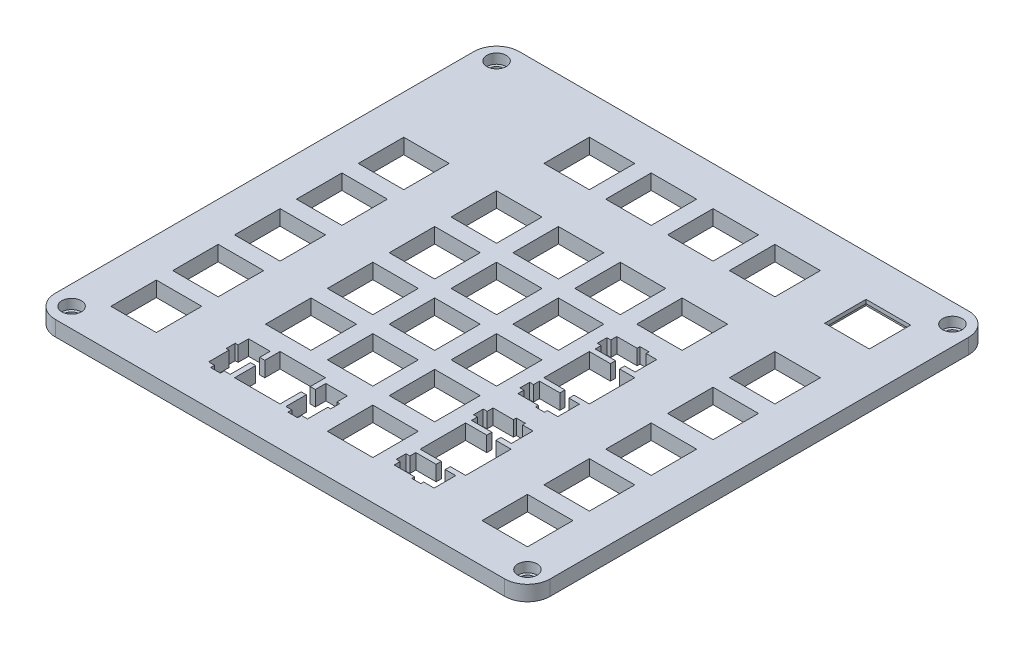
SolidWorks part; units mm, degrees
material "ABS"
ref_plane "Front Plane" through (0, 0, 0) normal (0, 0, 1) x (1, 0, 0)
ref_plane "Top Plane" through (0, 0, 0) normal (0, 1, 0) x (1, 0, 0)
ref_plane "Right Plane" through (0, 0, 0) normal (1, 0, 0) x (0, 0, -1)
sketch "Sketch6" plane through (0, 0, 0) normal (0, 1, 0) x (1, 0, 0)
  line L0 (7, 0) -> (145.39, 0)
  line L1 (152.39, 7) -> (152.39, 135.87)
  line L2 (7, 142.87) -> (145.39, 142.87)
  line L3 (0, 135.87) -> (0, 7)
  line L4 (54.62, 130.825) -> (40.62, 130.825)
  line L5 (40.62, 130.825) -> (40.62, 116.825)
  line L6 (40.62, 116.825) -> (54.62, 116.825)
  line L7 (54.62, 116.825) -> (54.62, 130.825)
  line L8 (73.67, 130.825) -> (59.67, 130.825)
  line L9 (59.67, 130.825) -> (59.67, 116.825)
  line L10 (59.67, 116.825) -> (73.67, 116.825)
  line L11 (73.67, 116.825) -> (73.67, 130.825)
  line L12 (92.72, 130.825) -> (78.72, 130.825)
  line L13 (78.72, 130.825) -> (78.72, 116.825)
  line L14 (78.72, 116.825) -> (92.72, 116.825)
  line L15 (92.72, 116.825) -> (92.72, 130.825)
  line L16 (111.77, 130.825) -> (97.77, 130.825)
  line L17 (97.77, 130.825) -> (97.77, 116.825)
  line L18 (97.77, 116.825) -> (111.77, 116.825)
  line L19 (111.77, 116.825) -> (111.77, 130.825)
  line L20 (26.045, 102.25) -> (12.045, 102.25)
  line L21 (12.045, 102.25) -> (12.045, 88.25)
  line L22 (12.045, 88.25) -> (26.045, 88.25)
  line L23 (26.045, 88.25) -> (26.045, 102.25)
  line L24 (54.62, 102.25) -> (40.62, 102.25)
  line L25 (40.62, 102.25) -> (40.62, 88.25)
  line L26 (40.62, 88.25) -> (54.62, 88.25)
  line L27 (54.62, 88.25) -> (54.62, 102.25)
  line L28 (73.67, 102.25) -> (59.67, 102.25)
  line L29 (59.67, 102.25) -> (59.67, 88.25)
  line L30 (59.67, 88.25) -> (73.67, 88.25)
  line L31 (73.67, 88.25) -> (73.67, 102.25)
  line L32 (92.72, 102.25) -> (78.72, 102.25)
  line L33 (78.72, 102.25) -> (78.72, 88.25)
  line L34 (78.72, 88.25) -> (92.72, 88.25)
  line L35 (92.72, 88.25) -> (92.72, 102.25)
  line L36 (111.77, 102.25) -> (97.77, 102.25)
  line L37 (97.77, 102.25) -> (97.77, 88.25)
  line L38 (97.77, 88.25) -> (111.77, 88.25)
  line L39 (111.77, 88.25) -> (111.77, 102.25)
  line L40 (140.345, 102.25) -> (126.345, 102.25)
  line L41 (126.345, 102.25) -> (126.345, 88.25)
  line L42 (126.345, 88.25) -> (140.345, 88.25)
  line L43 (140.345, 88.25) -> (140.345, 102.25)
  line L44 (26.045, 83.2) -> (12.045, 83.2)
  line L45 (12.045, 83.2) -> (12.045, 69.2)
  line L46 (12.045, 69.2) -> (26.045, 69.2)
  line L47 (26.045, 69.2) -> (26.045, 83.2)
  line L48 (54.62, 83.2) -> (40.62, 83.2)
  line L49 (40.62, 83.2) -> (40.62, 69.2)
  line L50 (40.62, 69.2) -> (54.62, 69.2)
  line L51 (54.62, 69.2) -> (54.62, 83.2)
  line L52 (73.67, 83.2) -> (59.67, 83.2)
  line L53 (59.67, 83.2) -> (59.67, 69.2)
  line L54 (59.67, 69.2) -> (73.67, 69.2)
  line L55 (73.67, 69.2) -> (73.67, 83.2)
  line L56 (92.72, 83.2) -> (78.72, 83.2)
  line L57 (78.72, 83.2) -> (78.72, 69.2)
  line L58 (78.72, 69.2) -> (92.72, 69.2)
  line L59 (92.72, 69.2) -> (92.72, 83.2)
  line L60 (98, 77.075) -> (98, 75.25)
  line L61 (98, 75.25) -> (104.27, 75.25)
  line L62 (104.27, 75.25) -> (104.27, 73.675)
  line L63 (104.27, 73.675) -> (97.77, 73.675)
  line L64 (97.77, 73.675) -> (97.77, 59.675)
  line L65 (97.77, 59.675) -> (104.27, 59.675)
  line L66 (104.27, 59.675) -> (104.27, 58.1)
  line L67 (104.27, 58.1) -> (98, 58.1)
  line L68 (98, 58.1) -> (98, 56.275)
  line L69 (98, 56.275) -> (96.8, 56.275)
  line L70 (96.8, 56.275) -> (96.8, 53.275)
  line L71 (96.8, 53.275) -> (98, 53.275)
  line L72 (98, 53.275) -> (98, 51.45)
  line L73 (98, 51.45) -> (104.27, 51.45)
  line L74 (104.27, 51.45) -> (104.27, 50.575)
  line L75 (104.27, 50.575) -> (107.07, 50.575)
  line L76 (107.07, 50.575) -> (107.07, 51.45)
  line L77 (107.07, 51.45) -> (110.3, 51.45)
  line L78 (110.3, 51.45) -> (110.3, 58.1)
  line L79 (110.3, 58.1) -> (107.07, 58.1)
  line L80 (107.07, 58.1) -> (107.07, 59.675)
  line L81 (107.07, 59.675) -> (111.77, 59.675)
  line L82 (111.77, 59.675) -> (111.77, 73.675)
  line L83 (111.77, 73.675) -> (107.07, 73.675)
  line L84 (107.07, 73.675) -> (107.07, 75.25)
  line L85 (107.07, 75.25) -> (110.3, 75.25)
  line L86 (110.3, 75.25) -> (110.3, 81.9)
  line L87 (110.3, 81.9) -> (107.07, 81.9)
  line L88 (107.07, 81.9) -> (107.07, 82.775)
  line L89 (107.07, 82.775) -> (104.27, 82.775)
  line L90 (104.27, 82.775) -> (104.27, 81.9)
  line L91 (104.27, 81.9) -> (98, 81.9)
  line L92 (98, 81.9) -> (98, 80.075)
  line L93 (98, 80.075) -> (96.8, 80.075)
  line L94 (96.8, 80.075) -> (96.8, 77.075)
  line L95 (96.8, 77.075) -> (98, 77.075)
  line L96 (140.345, 83.2) -> (126.345, 83.2)
  line L97 (126.345, 83.2) -> (126.345, 69.2)
  line L98 (126.345, 69.2) -> (140.345, 69.2)
  line L99 (140.345, 69.2) -> (140.345, 83.2)
  line L100 (26.045, 64.15) -> (12.045, 64.15)
  line L101 (12.045, 64.15) -> (12.045, 50.15)
  line L102 (12.045, 50.15) -> (26.045, 50.15)
  line L103 (26.045, 50.15) -> (26.045, 64.15)
  line L104 (54.62, 64.15) -> (40.62, 64.15)
  line L105 (40.62, 64.15) -> (40.62, 50.15)
  line L106 (40.62, 50.15) -> (54.62, 50.15)
  line L107 (54.62, 50.15) -> (54.62, 64.15)
  line L108 (73.67, 64.15) -> (59.67, 64.15)
  line L109 (59.67, 64.15) -> (59.67, 50.15)
  line L110 (59.67, 50.15) -> (73.67, 50.15)
  line L111 (73.67, 50.15) -> (73.67, 64.15)
  line L112 (92.72, 64.15) -> (78.72, 64.15)
  line L113 (78.72, 64.15) -> (78.72, 50.15)
  line L114 (78.72, 50.15) -> (92.72, 50.15)
  line L115 (92.72, 50.15) -> (92.72, 64.15)
  line L116 (140.345, 64.15) -> (126.345, 64.15)
  line L117 (126.345, 64.15) -> (126.345, 50.15)
  line L118 (126.345, 50.15) -> (140.345, 50.15)
  line L119 (140.345, 50.15) -> (140.345, 64.15)
  line L120 (26.045, 45.1) -> (12.045, 45.1)
  line L121 (12.045, 45.1) -> (12.045, 31.1)
  line L122 (12.045, 31.1) -> (26.045, 31.1)
  line L123 (26.045, 31.1) -> (26.045, 45.1)
  line L124 (54.62, 45.1) -> (40.62, 45.1)
  line L125 (40.62, 45.1) -> (40.62, 31.1)
  line L126 (40.62, 31.1) -> (54.62, 31.1)
  line L127 (54.62, 31.1) -> (54.62, 45.1)
  line L128 (73.67, 45.1) -> (59.67, 45.1)
  line L129 (59.67, 45.1) -> (59.67, 31.1)
  line L130 (59.67, 31.1) -> (73.67, 31.1)
  line L131 (73.67, 31.1) -> (73.67, 45.1)
  line L132 (92.72, 45.1) -> (78.72, 45.1)
  line L133 (78.72, 45.1) -> (78.72, 31.1)
  line L134 (78.72, 31.1) -> (92.72, 31.1)
  line L135 (92.72, 31.1) -> (92.72, 45.1)
  line L136 (98, 38.975) -> (98, 37.15)
  line L137 (98, 37.15) -> (104.27, 37.15)
  line L138 (104.27, 37.15) -> (104.27, 35.575)
  line L139 (104.27, 35.575) -> (97.77, 35.575)
  line L140 (97.77, 35.575) -> (97.77, 21.575)
  line L141 (97.77, 21.575) -> (104.27, 21.575)
  line L142 (104.27, 21.575) -> (104.27, 20)
  line L143 (104.27, 20) -> (98, 20)
  line L144 (98, 20) -> (98, 18.175)
  line L145 (98, 18.175) -> (96.8, 18.175)
  line L146 (96.8, 18.175) -> (96.8, 15.175)
  line L147 (96.8, 15.175) -> (98, 15.175)
  line L148 (98, 15.175) -> (98, 13.35)
  line L149 (98, 13.35) -> (104.27, 13.35)
  line L150 (104.27, 13.35) -> (104.27, 12.475)
  line L151 (104.27, 12.475) -> (107.07, 12.475)
  line L152 (107.07, 12.475) -> (107.07, 13.35)
  line L153 (107.07, 13.35) -> (110.3, 13.35)
  line L154 (110.3, 13.35) -> (110.3, 20)
  line L155 (110.3, 20) -> (107.07, 20)
  line L156 (107.07, 20) -> (107.07, 21.575)
  line L157 (107.07, 21.575) -> (111.77, 21.575)
  line L158 (111.77, 21.575) -> (111.77, 35.575)
  line L159 (111.77, 35.575) -> (107.07, 35.575)
  line L160 (107.07, 35.575) -> (107.07, 37.15)
  line L161 (107.07, 37.15) -> (110.3, 37.15)
  line L162 (110.3, 37.15) -> (110.3, 43.8)
  line L163 (110.3, 43.8) -> (107.07, 43.8)
  line L164 (107.07, 43.8) -> (107.07, 44.675)
  line L165 (107.07, 44.675) -> (104.27, 44.675)
  line L166 (104.27, 44.675) -> (104.27, 43.8)
  line L167 (104.27, 43.8) -> (98, 43.8)
  line L168 (98, 43.8) -> (98, 41.975)
  line L169 (98, 41.975) -> (96.8, 41.975)
  line L170 (96.8, 41.975) -> (96.8, 38.975)
  line L171 (96.8, 38.975) -> (98, 38.975)
  line L172 (140.345, 45.1) -> (126.345, 45.1)
  line L173 (126.345, 45.1) -> (126.345, 31.1)
  line L174 (126.345, 31.1) -> (140.345, 31.1)
  line L175 (140.345, 31.1) -> (140.345, 45.1)
  line L176 (26.045, 26.05) -> (12.045, 26.05)
  line L177 (12.045, 26.05) -> (12.045, 12.05)
  line L178 (12.045, 12.05) -> (26.045, 12.05)
  line L179 (26.045, 12.05) -> (26.045, 26.05)
  line L180 (46.745, 12.28) -> (48.57, 12.28)
  line L181 (48.57, 12.28) -> (48.57, 18.55)
  line L182 (48.57, 18.55) -> (50.145, 18.55)
  line L183 (50.145, 18.55) -> (50.145, 12.05)
  line L184 (50.145, 12.05) -> (64.145, 12.05)
  line L185 (64.145, 12.05) -> (64.145, 18.55)
  line L186 (64.145, 18.55) -> (65.72, 18.55)
  line L187 (65.72, 18.55) -> (65.72, 12.28)
  line L188 (65.72, 12.28) -> (67.545, 12.28)
  line L189 (67.545, 12.28) -> (67.545, 11.08)
  line L190 (67.545, 11.08) -> (70.545, 11.08)
  line L191 (70.545, 11.08) -> (70.545, 12.28)
  line L192 (70.545, 12.28) -> (72.37, 12.28)
  line L193 (72.37, 12.28) -> (72.37, 18.55)
  line L194 (72.37, 18.55) -> (73.245, 18.55)
  line L195 (73.245, 18.55) -> (73.245, 21.35)
  line L196 (73.245, 21.35) -> (72.37, 21.35)
  line L197 (72.37, 21.35) -> (72.37, 24.58)
  line L198 (72.37, 24.58) -> (65.72, 24.58)
  line L199 (65.72, 24.58) -> (65.72, 21.35)
  line L200 (65.72, 21.35) -> (64.145, 21.35)
  line L201 (64.145, 21.35) -> (64.145, 26.05)
  line L202 (64.145, 26.05) -> (50.145, 26.05)
  line L203 (50.145, 26.05) -> (50.145, 21.35)
  line L204 (50.145, 21.35) -> (48.57, 21.35)
  line L205 (48.57, 21.35) -> (48.57, 24.58)
  line L206 (48.57, 24.58) -> (41.92, 24.58)
  line L207 (41.92, 24.58) -> (41.92, 21.35)
  line L208 (41.92, 21.35) -> (41.045, 21.35)
  line L209 (41.045, 21.35) -> (41.045, 18.55)
  line L210 (41.045, 18.55) -> (41.92, 18.55)
  line L211 (41.92, 18.55) -> (41.92, 12.28)
  line L212 (41.92, 12.28) -> (43.745, 12.28)
  line L213 (43.745, 12.28) -> (43.745, 11.08)
  line L214 (43.745, 11.08) -> (46.745, 11.08)
  line L215 (46.745, 11.08) -> (46.745, 12.28)
  line L216 (92.72, 26.05) -> (78.72, 26.05)
  line L217 (78.72, 26.05) -> (78.72, 12.05)
  line L218 (78.72, 12.05) -> (92.72, 12.05)
  line L219 (92.72, 12.05) -> (92.72, 26.05)
  line L220 (140.345, 26.05) -> (126.345, 26.05)
  line L221 (126.345, 26.05) -> (126.345, 12.05)
  line L222 (126.345, 12.05) -> (140.345, 12.05)
  line L223 (140.345, 12.05) -> (140.345, 26.05)
  line L224 (135.34, 123.82) -> (131.34, 123.82) construction
  line L225 (133.34, 121.82) -> (133.34, 125.82) construction
  line L228 (76.195, 0) -> (76.195, 142.87) construction
  line L229 (0, 71.435) -> (152.39, 71.435) construction
  line L230 (5.995, 134.725) -> (5.995, 139.025) construction
  line L231 (8.145, 136.875) -> (3.845, 136.875) construction
  line L232 (144.245, 136.875) -> (148.545, 136.875) construction
  line L233 (146.395, 134.725) -> (146.395, 139.025) construction
  line L234 (144.245, 5.995) -> (148.545, 5.995) construction
  line L235 (146.395, 8.145) -> (146.395, 3.845) construction
  line L236 (8.145, 5.995) -> (3.845, 5.995) construction
  line L237 (5.995, 8.145) -> (5.995, 3.845) construction
  circle A0 centre (19.045, 19.05) radius 2
  circle A1 centre (19.045, 38.1) radius 2
  circle A2 centre (19.045, 57.15) radius 2
  circle A4 centre (19.045, 76.2) radius 2
  circle A5 centre (19.045, 95.25) radius 2
  circle A6 centre (85.72, 95.25) radius 2
  circle A7 centre (85.72, 57.15) radius 2
  circle A8 centre (85.72, 76.2) radius 2
  circle A9 centre (85.72, 19.05) radius 2
  circle A10 centre (85.72, 38.1) radius 2
  circle A11 centre (133.345, 19.05) radius 2
  circle A12 centre (133.345, 95.25) radius 2
  circle A13 centre (133.345, 38.1) radius 2
  circle A14 centre (133.345, 57.15) radius 2
  circle A15 centre (133.345, 76.2) radius 2
  circle A16 centre (66.67, 57.15) radius 2
  circle A17 centre (66.67, 76.2) radius 2
  circle A18 centre (66.67, 95.25) radius 2
  circle A19 centre (66.67, 38.1) radius 2
  circle A20 centre (47.62, 95.25) radius 2
  circle A21 centre (47.62, 76.2) radius 2
  circle A22 centre (47.62, 38.1) radius 2
  circle A23 centre (47.62, 57.15) radius 2
  circle A24 centre (104.77, 95.25) radius 2
  circle A25 centre (66.67, 123.825) radius 2
  circle A26 centre (85.72, 123.825) radius 2
  circle A27 centre (104.77, 123.825) radius 2
  circle A28 centre (47.62, 123.825) radius 2
  circle A29 centre (57.145, 19.05) radius 2
  circle A30 centre (104.77, 28.575) radius 2
  circle A31 centre (104.77, 66.675) radius 2
  arc A32 (145.39, 0) -> (152.39, 7) centre (145.39, 7) ccw
  arc A33 (7, 0) -> (0, 7) centre (7, 7) cw
  arc A34 (7, 142.87) -> (0, 135.87) centre (7, 135.87) ccw
  arc A35 (152.39, 135.87) -> (145.39, 142.87) centre (145.39, 135.87) ccw
  circle A37 centre (133.34, 123.82) radius 2
  circle A38 centre (5.995, 136.875) radius 2.15
  circle A39 centre (146.395, 136.875) radius 2.15
  circle A40 centre (146.395, 5.995) radius 2.15
  circle A41 centre (5.995, 5.995) radius 2.15
  point P289 (152.39, 0)
  point P292 (0, 0)
  point P295 (0, 142.87)
  dimension "D4" = 4
  dimension "D5" = 7
  dimension "D11" = 4
  dimension "D12" = 4.3
  dimension "D1" = 14
  dimension "D2" = 152.39
  dimension "D3" = 142.87
  dimension "D9" = 19.05
  dimension "D10" = 19.05
  dimension "D13" = 70.2
  dimension "D14" = 65.44
sketch "Sketch8" [suppressed] plane through (0, 0, 0) normal (0, 1, 0) x (1, 0, 0)
  line L0 (7, 0) -> (145.39, 0)
  line L1 (152.39, 7) -> (152.39, 135.87)
  line L2 (7, 142.87) -> (145.39, 142.87)
  line L3 (0, 135.87) -> (0, 7)
  arc A32 (145.39, 0) -> (152.39, 7) centre (145.39, 7) ccw
  arc A33 (7, 0) -> (0, 7) centre (7, 7) cw
  arc A34 (7, 142.87) -> (0, 135.87) centre (7, 135.87) ccw
  arc A35 (152.39, 135.87) -> (145.39, 142.87) centre (145.39, 135.87) ccw
extrude "Boss-Extrude1" add sketch "Sketch6" along normal blind 4.68 contours L1 A35 L2 A34 L3 A33 L0 A32 A39 A38 A37 L7 L6 L5 L4 L11 L10 L9 L8 L15 L14 L13 L12 L19 L18 L17 L16 L23 L22 L21 L20 L27 L26 L25 L24 L31 L30 L29 L28 region at (76.1953, 0, -74.18)
sketch "Sketch15" plane through (0, 4.68, 0) normal (0, 1, 0) x (1, 0, 0)
  line L1 (126.465, 130.195) -> (140.215, 130.195)
  line L2 (126.465, 130.195) -> (126.465, 117.445)
  line L3 (126.465, 117.445) -> (140.215, 117.445)
  line L4 (140.215, 130.195) -> (140.215, 117.445)
  line L5 (126.465, 130.195) -> (140.215, 117.445) construction
  line L6 (126.465, 117.445) -> (140.215, 130.195) construction
  point P0 (133.34, 123.82)
  dimension "D1" = 13.75
  dimension "D2" = 12.75
extrude "Cut-Extrude1" cut sketch "Sketch15" against normal through all both and the other way through all
sketch "Sketch16" plane through (0, 0, 0) normal (0, -1, 0) x (1, 0, 0)
  line L0 (11.45, -119.58) -> (11.45, -123.58) construction
  line L1 (17.9, -119.58) -> (17.9, -123.58)
  line L2 (5, -119.58) -> (5, -123.58)
  line L4 (0, -135.87) -> (0, -7) construction
  line L5 (7, -142.87) -> (145.39, -142.87) construction
  arc A0 (17.9, -119.58) -> (5, -119.58) centre (11.45, -119.58) ccw
  arc A1 (5, -123.58) -> (17.9, -123.58) centre (11.45, -123.58) ccw
  point P2 (11.45, -121.58)
  dimension "D1" = 21.29
  dimension "D2" = 4
  dimension "D3" = 5
  dimension "D4" = 12.9
extrude "Cut-Extrude2" cut sketch "Sketch16" against normal blind 2
sketch "Sketch17" plane through (0, 4.68, 0) normal (0, 1, 0) x (1, 0, 0)
  circle A0 centre (5.995, 136.875) radius 3
  circle A1 centre (146.395, 136.875) radius 3
  circle A2 centre (146.395, 5.995) radius 3
  circle A3 centre (5.995, 5.995) radius 3
  dimension "D1" = 6
  dimension "D2" = 6
  dimension "D3" = 6
  dimension "D4" = 6
extrude "Cut-Extrude3" cut sketch "Sketch17" against normal blind 3 contours A3 | A2 | A1 | A0 region at (5.995, 4.68, -136.875) region at (146.395, 4.68, -136.875) region at (146.395, 4.68, -5.995) region at (5.995, 4.68, -5.995)
sketch "Sketch19" plane through (0, 0, 0) normal (0, -1, 0) x (1, 0, 0)
  line L0 (126.465, -130.195) -> (140.215, -117.445) construction
  line L1 (126.465, -117.445) -> (140.215, -130.195) construction
  line L2 (140.215, -117.445) -> (140.215, -130.195) construction
  line L3 (123.465, -114.445) -> (143.215, -114.445)
  line L4 (123.465, -114.445) -> (123.465, -133.195)
  line L5 (123.465, -133.195) -> (143.215, -133.195)
  line L6 (143.215, -114.445) -> (143.215, -133.195)
  line L7 (123.465, -114.445) -> (143.215, -133.195) construction
  line L8 (123.465, -133.195) -> (143.215, -114.445) construction
  line L9 (140.215, -130.195) -> (126.465, -130.195) construction
  point P8 (133.34, -123.82)
  dimension "D1" = 3
  dimension "D2" = 3
extrude "Cut-Extrude5" cut sketch "Sketch19" against normal blind 3.5
sketch "Sketch18" plane through (0, 0, 0) normal (0, -1, 0) x (1, 0, 0)
  line L0 (7, -142.87) -> (145.39, -142.87) construction
  line L1 (28.86, -134.44) -> (39, -134.44)
  line L2 (28.86, -134.44) -> (28.86, -142.87)
  line L3 (28.86, -142.87) -> (39, -142.87)
  line L4 (39, -134.44) -> (39, -142.87)
  line L5 (28.86, -134.44) -> (39, -142.87) construction
  line L6 (28.86, -142.87) -> (39, -134.44) construction
  line L8 (0, -135.87) -> (0, -7) construction
  point P0 (33.93, -138.655)
  dimension "D1" = 33.93
  dimension "D2" = 8.43
  dimension "D3" = 10.14
extrude "Cut-Extrude4" cut sketch "Sketch18" against normal blind 2
